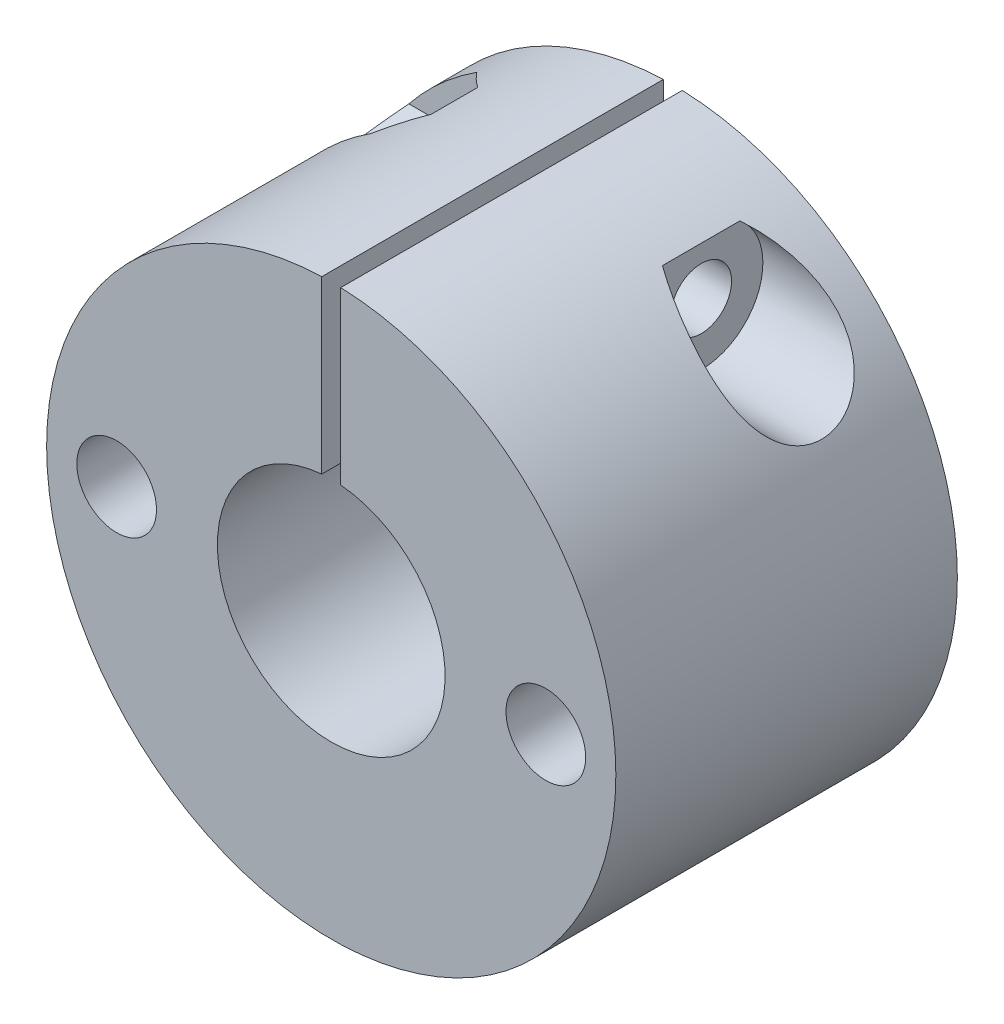
SolidWorks part; units mm, degrees
ref_plane "正面" through (0, 0, 0) normal (0, 0, 1) x (1, 0, 0)
ref_plane "平面" through (0, 0, 0) normal (0, 1, 0) x (1, 0, 0)
ref_plane "右側面" through (0, 0, 0) normal (1, 0, 0) x (0, 0, -1)
sketch "Sketch1" plane through (0, 0, 0) normal (0, 0, 1) x (1, 0, 0)
  circle A0 centre (0, 0) radius 6
  circle A1 centre (0, 0) radius 15
  dimension "D1" = 12
  dimension "D2" = 30
extrude "Boss-Extrude1" add sketch "Sketch1" along normal blind 10
sketch "Sketch2" plane through (0, 0, 10) normal (0, 0, 1) x (1, 0, 0)
  line L0 (0, 15) -> (0, 6) construction
  line L2 (-0.5, 18) -> (0.5, 18)
  line L3 (-0.5, 18) -> (-0.5, 3)
  line L4 (-0.5, 3) -> (0.5, 3)
  line L5 (0.5, 18) -> (0.5, 3)
  line L6 (-0.5, 18) -> (0.5, 3) construction
  line L7 (-0.5, 3) -> (0.5, 18) construction
  circle A0 centre (0, 0) radius 15 construction
  circle A1 centre (0, 0) radius 6 construction
  point P7 (0, 10.5)
  dimension "D1" = 1
  dimension "D2" = 15
extrude "Cut-Extrude1" cut sketch "Sketch2" against normal up to next
sketch "Sketch3" plane through (0.5, 0, 0) normal (-1, 0, 0) x (0, 0, 1)
  line L0 (0, 10.9917) -> (10, 10.9917) construction
  line L1 (0, 14.9917) -> (0, -15) construction
  line L2 (10, -15) -> (10, 14.9917) construction
  line L3 (0, 14.9917) -> (10, 14.9917) construction
  circle A0 centre (5, 10.9917) radius 1.6
  dimension "D1" = 3.2
  dimension "D2" = 4
extrude "Cut-Extrude2" cut sketch "Sketch3" against normal blind 30 and the other way blind 30
sketch "Sketch4" plane through (0.5, 0, 0) normal (-1, 0, 0) x (0, 0, 1)
  circle A0 centre (5, 10.9917) radius 3.25
  dimension "D1" = 6.5
extrude "Cut-Extrude3" cut sketch "Sketch4" against normal blind 30 from offset 6 offset against normal yes
sketch "Sketch5" plane through (-0.5, 0, 0) normal (1, 0, 0) x (0, 0, -1)
  line L1 (-2.2, 9.3751) -> (-2.2, 12.6082)
  line L2 (-2.2, 12.6082) -> (-5, 14.2248)
  line L3 (-5, 14.2248) -> (-7.8, 12.6082)
  line L4 (-7.8, 12.6082) -> (-7.8, 9.3751)
  line L5 (-7.8, 9.3751) -> (-5, 7.7585)
  line L6 (-5, 7.7585) -> (-2.2, 9.3751)
  circle A0 centre (-5, 10.9917) radius 2.8 construction
  dimension "D1" = 5.6
extrude "Cut-Extrude4" cut sketch "Sketch5" against normal blind 30 from offset 6 offset against normal yes
sketch "Sketch10" plane through (0, 0, 10) normal (0, 0, 1) x (1, 0, 0)
  line L0 (0, 0) -> (15, 0) construction
  line L1 (0, 0) -> (11.31, 0) construction
  arc A0 (-0.5, 14.9917) -> (0.5, 14.9917) centre (0, 0) ccw construction
  circle A1 centre (11.31, 0) radius 2.1
  circle A2 centre (-11.31, 0) radius 2.1
  dimension "D2" = 4.2
  dimension "D1" = 11.31
  dimension "D4" = 11.31
  dimension "D3" = 2
extrude "Cut-Extrude6" cut sketch "Sketch10" against normal up to next
sketch "Sketch11" plane through (0, 0, 10) normal (0, 0, 1) x (1, 0, 0)
  line L2 (0.5, 14.9917) -> (0.5, 5.9791)
  line L3 (-0.5, 5.9791) -> (-0.5, 14.9917)
  line L4 (0.5, 14.9917) -> (0.5, 5.9791)
  line L5 (-0.5, 5.9791) -> (-0.5, 14.9917)
  circle A0 centre (11.31, 0) radius 2.1 construction
  circle A1 centre (-11.31, 0) radius 2.1 construction
  arc A2 (-0.5, 5.9791) -> (0.5, 5.9791) centre (0, 0) ccw
  arc A3 (-0.5, 14.9917) -> (0.5, 14.9917) centre (0, 0) ccw
  arc A4 (-0.5, 5.9791) -> (0.5, 5.9791) centre (0, 0) ccw
  arc A5 (-0.5, 14.9917) -> (0.5, 14.9917) centre (0, 0) ccw
  circle A6 centre (11.31, 0) radius 2.1
  circle A7 centre (-11.31, 0) radius 2.1
  dimension "D1" = 0
extrude "Boss-Extrude3" add sketch "Sketch11" along normal blind 8
